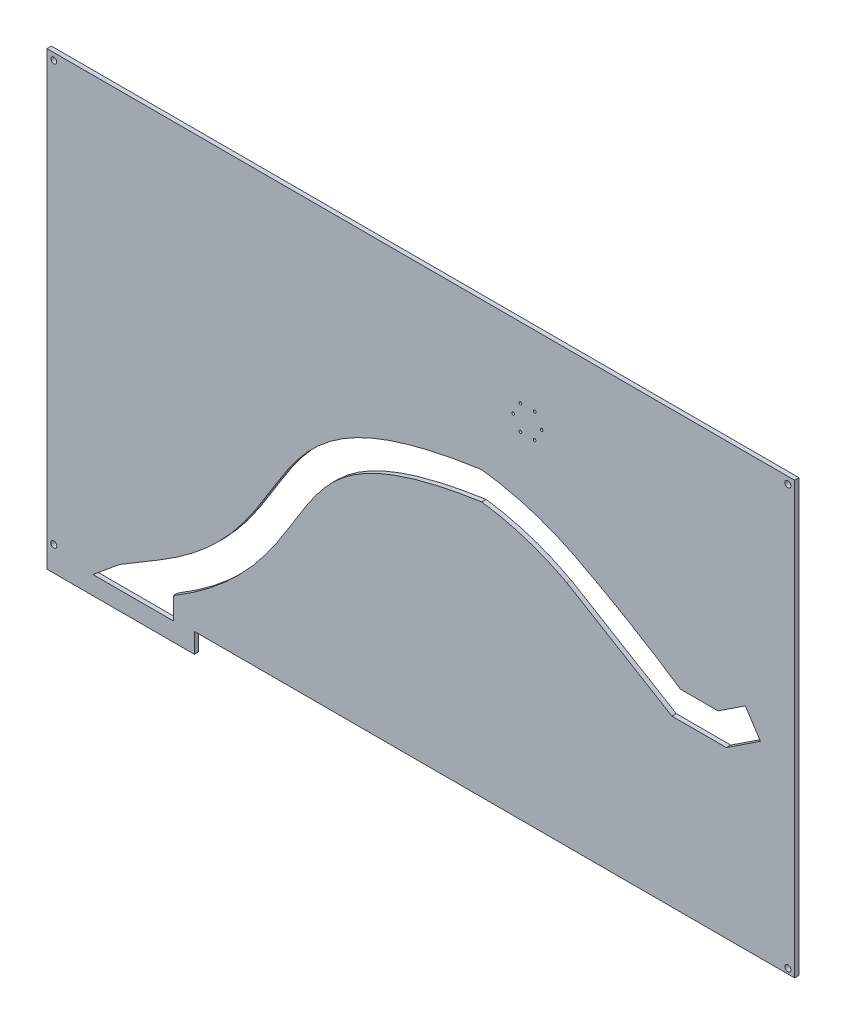
SolidWorks part; units mm, degrees
ref_plane "前视基准面" through (0, 0, 0) normal (0, 0, 1) x (1, 0, 0)
ref_plane "上视基准面" through (0, 0, 0) normal (0, 1, 0) x (1, 0, 0)
ref_plane "右视基准面" through (0, 0, 0) normal (1, 0, 0) x (0, 0, -1)
sketch "Sketch1" plane through (0, 0, 0) normal (0, 0, 1) x (1, 0, 0)
  line L0 (86.3892, 46.5642) -> (136.3892, 46.5642) construction
  line L1 (136.3892, 46.5642) -> (169.6686, 68.4983) construction
  line L2 (-475, -100) -> (-518.0311, -125.7444)
  line L3 (-459.5978, -125.7444) -> (-459.5978, -149.5504)
  line L4 (81.7745, 31.5642) -> (140.8878, 31.5642)
  line L5 (-467.2989, -112.8722) -> (-510.33, -138.6166) construction
  line L6 (140.8878, 31.5642) -> (177.9233, 55.9739)
  line L7 (-459.5978, -149.5504) -> (-546.7804, -149.5504)
  line L8 (-436.8168, -147.9944) -> (215.0808, -147.9944)
  line L9 (215.0808, -147.9944) -> (215.0808, 320)
  line L10 (215.0808, 320) -> (-596.8168, 320)
  line L11 (-596.8168, -150) -> (-596.8168, 320)
  line L12 (215.0808, -147.9944) -> (-596.8168, 320) construction
  line L13 (215.0808, 320) -> (-596.8168, -150) construction
  line L14 (-518.0311, -125.7444) -> (-459.5978, -125.7444) construction
  line L15 (-518.0311, -125.7444) -> (-546.7804, -149.5504)
  line L16 (-436.8168, -147.9944) -> (-436.8168, -169.5504)
  line L17 (90.9712, 61.5642) -> (131.8907, 61.5642)
  line L18 (-596.8168, -150) -> (-596.8168, -169.5504)
  line L19 (-596.8168, -169.5504) -> (-436.8168, -169.5504)
  line L21 (-32.3237, 100) -> (135.1953, 100) construction
  line L22 (-25, 130) -> (125, 130) construction
  line L23 (-28.6108, 115) -> (130.0228, 115) construction
  line L24 (131.8907, 61.5642) -> (161.4139, 81.0227)
  line L25 (177.9233, 55.9739) -> (161.4139, 81.0227)
  line L26 (-21.7014, 128.3139) -> (-25, 130)
  line L27 (-32.3237, 100) -> (81.7745, 31.5642)
  arc A0 (-125, 160) -> (-25, 130) centre (-159.8893, -137.9643) cw
  arc A1 (-28.6108, 115) -> (86.3892, 46.5642) centre (-559.3589, -907.7137) cw construction
  arc A2 (-124.7147, 129.7347) -> (-32.3237, 100) centre (-159.8893, -137.9643) cw
  circle A3 centre (-75, 230) radius 15.5 construction
  arc A4 (-124.84, 144.8723) -> (-28.6108, 115) centre (-159.8893, -137.9643) cw construction
  arc A5 (-21.7014, 128.3139) -> (90.9712, 61.5642) centre (-559.3589, -907.7137) cw
  circle A6 centre (-589.3757, -142.5578) radius 3.2924
  circle A7 centre (207.6422, -142.5578) radius 3.2924
  circle A8 centre (207.6422, 312.5578) radius 3.2944
  circle A9 centre (-589.3757, 312.5578) radius 3.1635
  arc A10 (135.1953, 100) -> (187.8618, 132.897) centre (303.6181, -111.0302) cw construction
  arc A11 (130.0228, 115) -> (181.4309, 146.4485) centre (303.6181, -111.0302) cw construction
  arc A12 (125, 130) -> (175, 160) centre (303.6181, -111.0302) cw construction
  arc A13 (-35.5202, 101.6861) -> (81.7745, 31.5642) centre (-559.3589, -907.7137) cw construction
  circle A14 centre (-90.5, 230) radius 1.5
  circle A15 centre (-82.75, 243.4234) radius 1.5
  circle A16 centre (-67.25, 243.4234) radius 1.5
  circle A17 centre (-59.5, 230) radius 1.5
  circle A18 centre (-67.25, 216.5766) radius 1.5
  circle A19 centre (-82.75, 216.5766) radius 1.5
  spline S0 degree 3 poles (-475, -100) (-419.5406, -66.8201) (-329.5908, 43.116) (-307.6356, 134.2871) (-125, 160) knots 0 0 0 0 0.312224 1 1 1 1
  spline S1 degree 1 poles (-459.5978, -125.7444) (-124.7147, 129.7347) knots 0 0 1 1 construction
  spline S2 degree 3 poles (-459.5978, -125.7444) (-458.1292, -124.8657) (-455.1858, -123.0815) (-449.4714, -119.5247) (-442.5555, -115.0462) (-434.6362, -109.6397) (-424.5564, -102.3861) (-412.8294, -93.2453) (-400.0558, -82.1905) (-388.4865, -71.0922) (-374.5374, -56.3046) (-359.6201, -37.9792) (-344.8908, -16.7676) (-332.3401, 3.2457) (-321.0552, 21.7964) (-310.226, 38.6648) (-299.0796, 53.8348) (-286.8128, 67.5146) (-272.4318, 80.0885) (-257.6527, 89.9241) (-243.4982, 97.442) (-231.5651, 102.8866) (-218.1727, 108.1127) (-203.191, 113.0878) (-189.2817, 116.9961) (-177.2434, 119.9629) (-167.7458, 122.1041) (-157.766, 124.1573) (-149.0369, 125.7919) (-141.7993, 127.0518) (-136.2431, 127.9723) (-131.5022, 128.7191) (-127.6487, 129.3032) (-125.6903, 129.5925) (-124.7147, 129.7347) knots 0 0 0 0 0.007773 0.015545 0.03109 0.046636 0.062181 0.093271 0.124361 0.155452 0.186542 0.248723 0.310904 0.373084 0.435265 0.497446 0.559626 0.621807 0.683988 0.746169 0.777259 0.808349 0.83944 0.87053 0.90162 0.917166 0.932711 0.948256 0.963801 0.971574 0.979346 0.987119 0.991005 0.994892 0.994892 0.994892 0.994892
  spline S3 degree 1 poles (-467.2989, -112.8722) (-124.84, 144.8723) knots 0 0 1 1 construction
  spline S4 degree 3 poles (-467.2989, -112.8722) (-465.8766, -112.0213) (-463.025, -110.2926) (-457.4973, -106.8516) (-450.8174, -102.5249) (-443.1848, -97.3122) (-433.4896, -90.3317) (-422.2436, -81.559) (-410.0336, -70.981) (-398.9994, -60.3828) (-385.707, -46.2708) (-371.4731, -28.7597) (-357.2741, -8.2881) (-344.9599, 11.3612) (-333.6257, 29.9919) (-322.417, 47.4318) (-310.4985, 63.6121) (-297.0179, 78.5777) (-281.0248, 92.4603) (-264.7088, 103.2127) (-249.3105, 111.3089) (-236.4572, 117.1105) (-222.1723, 122.621) (-206.3349, 127.8161) (-191.7467, 131.8615) (-179.1859, 134.915) (-169.3063, 137.1107) (-158.9544, 139.2089) (-149.9221, 140.8739) (-142.4479, 142.1541) (-136.7117, 143.0887) (-130.8627, 143.9946) (-126.8382, 144.5862) (-124.84, 144.8723) knots 0 0 0 0 0.007793 0.015586 0.031173 0.046759 0.062345 0.093518 0.12469 0.155863 0.187036 0.249381 0.311726 0.374071 0.436417 0.498762 0.561107 0.623452 0.685798 0.748143 0.779315 0.810488 0.841661 0.872833 0.904006 0.919592 0.935179 0.950765 0.966351 0.974144 0.981937 0.989731 0.997524 0.997524 0.997524 0.997524 construction
  point P38 (-190, 85.5025)
  point P62 (-75, 230)
  dimension "D5" = 300
  dimension "D8" = 15
  dimension "D14" = 470
  dimension "D18" = 70
  dimension "D22" = 651.8975
  dimension "D24" = 50
  dimension "D26" = 6
  dimension "D27" = 3
  dimension "D1" = 105
  dimension "D2" = 100
  dimension "D3" = 350
  dimension "D4" = 260
  dimension "D6" = 100
  dimension "D7" = 30
  dimension "D9" = 15
  dimension "D10" = 115
  dimension "D11" = 50
  dimension "D13" = 15
  dimension "D15" = 190
  dimension "D16" = 320
  dimension "D17" = 20
  dimension "D25" = 811.9
  dimension "D12" = 30
extrude "Boss-Extrude1" add sketch "Sketch1" along normal blind 4.7625
